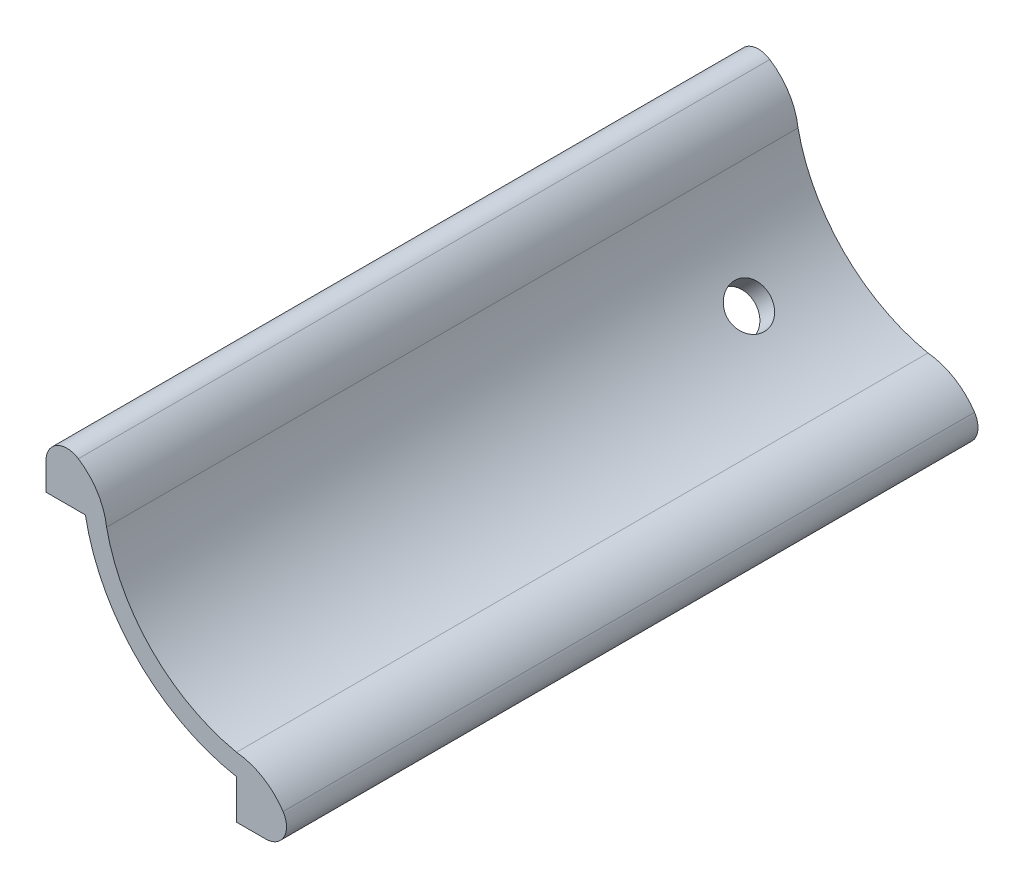
SolidWorks part; units mm, degrees
ref_plane "Front Plane" through (0, 0, 0) normal (0, 0, 1) x (1, 0, 0)
ref_plane "Top Plane" through (0, 0, 0) normal (0, 1, 0) x (1, 0, 0)
ref_plane "Right Plane" through (0, 0, 0) normal (1, 0, 0) x (0, 0, -1)
sketch "Sketch1" plane through (0, 0, 0) normal (0, 0, 1) x (1, 0, 0)
  line L4 (-45.7962, 45.7962) -> (0, 45.7962) construction
  line L6 (0, 45.7962) -> (0, 0) construction
  line L7 (-58.2422, 56.2102) -> (-58.2422, 62.5602)
  line L8 (10.922, -12.446) -> (17.272, -12.446)
  line L9 (-58.2422, 56.2102) -> (-58.2422, 45.7962) construction
  line L10 (-58.2422, 45.7962) -> (-45.7962, 45.7962) construction
  line L11 (0, 0) -> (0, -12.446) construction
  line L12 (0, -12.446) -> (10.922, -12.446) construction
  arc A6 (0, 0) -> (-45.7962, 45.7962) centre (10.3996, 56.1958) cw
  arc A7 (-45.7962, 45.7962) -> (-58.2422, 56.2102) centre (-58.3145, 43.4796) ccw
  arc A8 (0, 0) -> (10.922, -12.446) centre (-1.8079, -12.6018) cw
  arc A9 (-58.2422, 62.5602) -> (-39.3749, 45.7962) centre (-58.3145, 43.4796) cw
  arc A10 (-39.3749, 45.7962) -> (0, 6.4213) centre (10.3996, 56.1958) ccw
  arc A11 (0, 6.4213) -> (17.272, -12.446) centre (-1.8793, -12.6385) cw
  dimension "D1" = 45.7962
  dimension "D2" = 57.15
  dimension "D3" = 10.414
  dimension "D5" = 12.446
  dimension "D4" = 6.35
  dimension "D6" = 12.446
  dimension "D7" = 10.922
extrude "Boss-Extrude1" add sketch "Sketch1" along normal mid plane 209.55 contours L4 | A11 L8 A8 A6 A7 L7 A9 A10 region at (-42.5855, 44.9377, 0)
sketch "Sketch2" plane through (0, 0, 0) normal (0, 0, 1) x (1, 0, 0)
  line L0 (-58.2422, 56.2102) -> (-58.2422, 45.7962)
  line L1 (-58.2422, 45.7962) -> (-45.7962, 45.7962)
  line L2 (0, 0) -> (0, -12.446)
  line L3 (0, -12.446) -> (10.922, -12.446)
  arc A0 (-45.7962, 45.7962) -> (-58.2422, 56.2102) centre (-58.3145, 43.4796) ccw construction
  arc A1 (-45.7962, 45.7962) -> (0, 0) centre (10.3996, 56.1958) ccw construction
  arc A2 (-58.2422, 56.2102) -> (-45.7962, 45.7962) centre (-58.3145, 43.4796) cw
  arc A3 (0, 0) -> (10.922, -12.446) centre (-1.8079, -12.6018) cw
extrude "Boss-Extrude2" add sketch "Sketch2" along normal mid plane 185.1914
sketch "Sketch3" plane through (0, 0, -104.775) normal (0, 0, -1) x (-1, 0, 0)
  line L0 (58.2422, 56.2102) -> (58.2422, 45.7962)
  line L1 (58.2422, 45.7962) -> (45.7962, 45.7962)
  line L2 (0, 0) -> (0, -12.446)
  line L3 (0, -12.446) -> (-10.922, -12.446)
  arc A0 (-10.922, -12.446) -> (0, 0) centre (1.8079, -12.6018) cw
  arc A1 (45.7962, 45.7962) -> (58.2422, 56.2102) centre (58.3145, 43.4796) cw
extrude "Boss-Extrude3" add sketch "Sketch3" against normal offset from surface (5.8293 mm away) 6.35 up to face at (-53.4687, 50.0142, -92.5957)
sketch "Sketch4" plane through (0, 0, 104.775) normal (0, 0, 1) x (1, 0, 0)
  line L0 (-58.2422, 56.2102) -> (-58.2422, 45.7962)
  line L1 (-58.2422, 45.7962) -> (-45.7962, 45.7962)
  line L2 (0, 0) -> (0, -12.446)
  line L3 (0, -12.446) -> (10.922, -12.446)
  arc A0 (-58.2422, 56.2102) -> (-45.7962, 45.7962) centre (-58.3145, 43.4796) cw
  arc A1 (0, 0) -> (10.922, -12.446) centre (-1.8079, -12.6018) cw
extrude "Boss-Extrude4" add sketch "Sketch4" against normal blind 6.35
sketch "Sketch5" plane through (0, 0, 104.775) normal (0, 0, 1) x (1, 0, 0)
  line L0 (-58.2422, 45.7962) -> (-58.2422, 62.5602) construction
  line L2 (-57.7342, 44.7636) -> (-65.5217, 44.7636)
  line L3 (-57.7342, 44.7636) -> (-57.7342, 64.5974)
  line L4 (-57.7342, 64.5974) -> (-65.5217, 64.5974)
  line L5 (-65.5217, 44.7636) -> (-65.5217, 64.5974)
  line L6 (-3.152, -11.938) -> (19.6021, -11.938)
  line L7 (-3.152, -11.938) -> (-3.152, -15.345)
  line L8 (-3.152, -15.345) -> (19.6021, -15.345)
  line L9 (19.6021, -11.938) -> (19.6021, -15.345)
  line L10 (0, -12.446) -> (17.272, -12.446) construction
  dimension "D1" = 0.508
  dimension "D2" = 0.508
extrude "Cut-Extrude1" cut sketch "Sketch5" against normal through all
fillet "Fillet1" radius 6.35 2 edges at (17.2602, -11.938, 0) (-57.7342, 62.5515, 0)
ref_plane "Plane1" through (-5.969, -5.969, 0) normal (-0.7071, -0.7071, 0) x (-0.7071, 0.7071, 0)
sketch "Sketch6" plane through (-5.969, -5.969, 0) normal (-0.7071, -0.7071, 0) x (-0.7071, 0.7071, 0)
  line L0 (0, 75.9801) -> (64.7656, 75.9801) construction
  line L1 (0, -92.5957) -> (0, 92.5957) construction
  line L2 (64.7656, -92.5957) -> (64.7656, 92.5957) construction
  circle A0 centre (32.3828, 75.9801) radius 6.35
  point P2 (32.4579, 71.6327)
  point P9 (32.3828, 75.9801)
  dimension "D1" = 12.7
extrude "Cut-Extrude2" cut sketch "Sketch6" against normal mid plane 12.7
